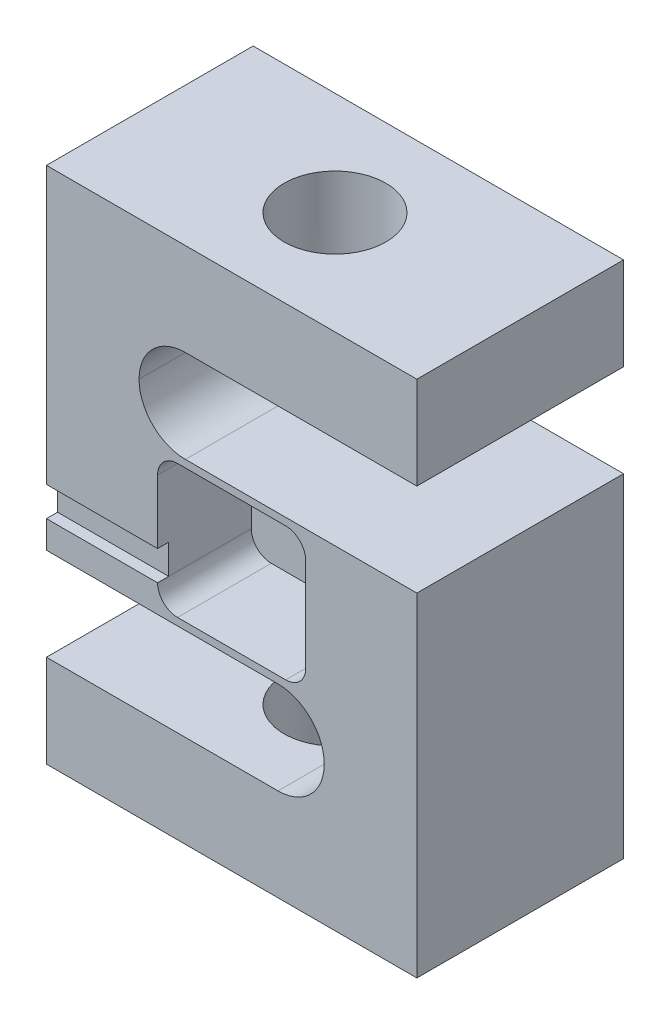
SolidWorks part; units mm, degrees
material "AISI 4340 Steel, normalized"
ref_plane "Front Plane" through (0, 0, 0) normal (0, 0, 1) x (1, 0, 0)
ref_plane "Top Plane" through (0, 0, 0) normal (0, 1, 0) x (1, 0, 0)
ref_plane "Right Plane" through (0, 0, 0) normal (1, 0, 0) x (0, 0, -1)
sketch "Sketch1" plane through (0, 0, 0) normal (0, 0, 1) x (1, 0, 0)
  line L0 (47.625, 0) -> (0, 0)
  line L1 (47.625, 0) -> (47.625, -57.15)
  line L2 (47.625, -57.15) -> (-15.875, -57.15)
  line L3 (-15.875, -57.15) -> (-15.875, -41.275)
  line L4 (-15.875, -41.275) -> (31.75, -41.275)
  line L5 (31.75, -41.275) -> (31.75, -25.4)
  line L6 (31.75, -25.4) -> (-15.875, -25.4)
  line L7 (-15.875, -25.4) -> (-15.875, 31.75)
  line L8 (-15.875, 31.75) -> (47.625, 31.75)
  line L9 (47.625, 31.75) -> (47.625, 15.875)
  line L10 (47.625, 15.875) -> (0, 15.875)
  line L11 (0, 15.875) -> (0, 0)
  dimension "D1" = 25.4
  dimension "D2" = 15.875
  dimension "D4" = 15.875
  dimension "D5" = 63.5
extrude "Boss-Extrude1" add sketch "Sketch1" along normal mid plane 35.433
fillet "Fillet1" radius 7.9375 4 edges at (31.75, -41.275, 0) (31.75, -25.4, 0) (0, 15.875, 0) (0, 0, 0)
sketch "Sketch2" plane through (0, 31.75, 0) normal (0, 1, 0) x (1, 0, 0)
  line L0 (15.875, 17.7165) -> (15.875, -17.7165) construction
  line L1 (47.625, 17.7165) -> (-15.875, 17.7165) construction
  line L2 (47.625, -17.7165) -> (-15.875, -17.7165) construction
  point P6 (15.875, 0)
sketch "Sketch3" plane through (0, -57.15, 0) normal (0, -1, 0) x (1, 0, 0)
  line L0 (15.875, 17.7165) -> (15.875, -17.7165) construction
  line L1 (-15.875, 17.7165) -> (47.625, 17.7165) construction
  line L2 (-15.875, -17.7165) -> (47.625, -17.7165) construction
  point P6 (15.875, 0)
hole_wizard "3/4-16 Tapped Hole1" positions "Sketch5" profile "Sketch4" tap size "3/4-16" standard "Ansi Inch" end condition up to next
sketch "Sketch5" plane through (0, -57.15, 0) normal (0, -1, 0) x (1, 0, 0)
  point P1 (15.875, 0)
sketch "Sketch4" plane through (15.875, -57.15, 0) normal (1, 0, 0) x (0, 0, -1)
  line L0 (0, 0) -> (0, 15.875)
  line L1 (0, 15.875) -> (8.7312, 15.875)
  line L2 (8.7312, 15.875) -> (8.7312, 0)
  line L5 (8.7312, 0) -> (0, 0)
  line L11 (0, -6.35) -> (0, 107.95) construction
  dimension "Thru Tap Drill Dia." = 17.4625
  dimension "Thru Tap Drill Depth" = 15.875
cosmetic thread "Hole Thread3" parameters "D2"=19.05
hole_wizard "3/4-16 Tapped Hole2" positions "Sketch7" profile "Sketch6" tap size "3/4-16" standard "Ansi Inch" end condition up to next
sketch "Sketch7" plane through (0, 31.75, 0) normal (0, 1, 0) x (-1, 0, 0)
  point P1 (-15.875, 0)
sketch "Sketch6" plane through (15.875, 31.75, 0) normal (1, 0, 0) x (0, 0, 1)
  line L0 (0, 0) -> (0, 15.875)
  line L1 (0, 15.875) -> (8.7312, 15.875)
  line L2 (8.7312, 15.875) -> (8.7312, 0)
  line L5 (8.7312, 0) -> (0, 0)
  line L11 (0, -6.35) -> (0, 107.95) construction
  dimension "Thru Tap Drill Dia." = 17.4625
  dimension "Thru Tap Drill Depth" = 15.875
cosmetic thread "Hole Thread4" parameters "D2"=19.05
sketch "Sketch8" plane through (0, 0, 17.7165) normal (0, 0, 1) x (1, 0, 0)
  line L0 (15.875, 31.75) -> (15.875, -1.27) construction
  line L1 (3.175, -24.13) -> (28.575, -24.13)
  line L2 (3.175, -24.13) -> (3.175, -1.27)
  line L3 (3.175, -1.27) -> (28.575, -1.27)
  line L4 (28.575, -24.13) -> (28.575, -1.27)
  line L5 (3.175, -24.13) -> (28.575, -1.27) construction
  line L6 (3.175, -1.27) -> (28.575, -24.13) construction
  line L7 (47.625, 31.75) -> (-15.875, 31.75) construction
  line L8 (28.575, -1.27) -> (28.575, 0) construction
  line L9 (47.625, 0) -> (7.9375, 0) construction
  line L10 (3.175, -24.13) -> (3.175, -25.4) construction
  line L11 (-15.875, -25.4) -> (23.8125, -25.4) construction
  point P0 (15.875, -12.7)
  dimension "D1" = 1.27
  dimension "D2" = 25.4
  dimension "D3" = 22.86
extrude "Cut-Extrude1" cut sketch "Sketch8" against normal blind 16.0655
fillet "Fillet2" radius 3.429 4 edges at (3.175, -24.13, 9.6837) (28.575, -24.13, 9.6837) (28.575, -1.27, 9.6837) (3.175, -1.27, 9.6837)
mirror "Mirror1" about plane through (0, 0, 0) normal (0, 0, 1) of "Cut-Extrude1", "Fillet2"
sketch "Sketch10" plane through (0, 0, 1.651) normal (0, 0, 1) x (1, 0, 0)
  line L0 (15.875, -1.27) -> (15.875, -12.7) construction
  line L1 (25.146, -1.27) -> (6.604, -1.27) construction
  line L2 (15.875, -12.7) -> (15.875, -24.13) construction
  line L3 (6.604, -24.13) -> (25.146, -24.13) construction
  circle A0 centre (15.875, -12.7) radius 1.27
  dimension "D1" = 2.54
extrude "Boss-Extrude2" add sketch "Sketch10" along normal blind 0.254
mirror "Mirror2" about plane through (0, 0, 0) normal (0, 0, 1) of "Boss-Extrude2"
sketch "Sketch11" plane through (-15.875, 0, 0) normal (-1, 0, 0) x (0, 0, 1)
  line L0 (0, -25.4) -> (0, -19.05) construction
  line L1 (17.7165, -25.4) -> (-17.7165, -25.4) construction
  dimension "D1" = 6.35
sketch "Sketch15" plane through (0, 0, 17.7165) normal (0, 0, 1) x (1, 0, 0)
  line L0 (-15.875, 31.75) -> (-15.875, -25.4) construction
  line L1 (3.175, -20.701) -> (-15.875, -20.701)
  line L2 (3.175, -20.701) -> (3.175, -15.621)
  line L3 (3.175, -15.621) -> (-15.875, -15.621)
  line L4 (-15.875, -20.701) -> (-15.875, -15.621)
  dimension "D1" = 5.08
extrude "Cut-Extrude2" cut sketch "Sketch15" against normal blind 1.905
sketch "Sketch16" plane through (0, 31.75, 0) normal (0, 1, 0) x (1, 0, 0)
  line L0 (47.625, -17.7165) -> (47.625, -43.1165) construction
  dimension "D1" = 25.4
